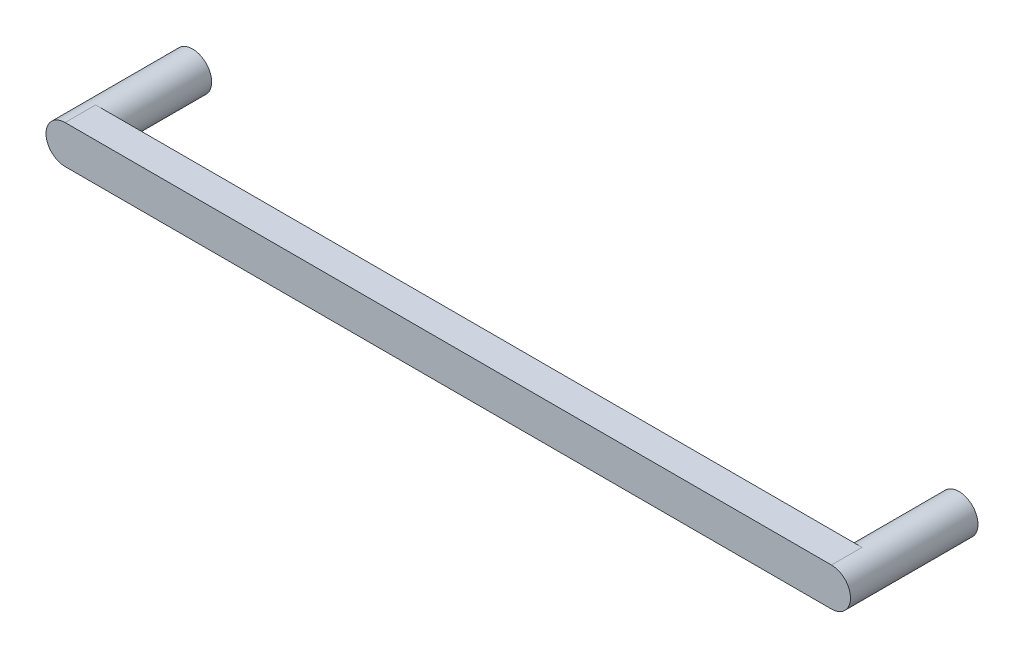
SolidWorks part; units mm, degrees
material "PLA 100% Infill"
ref_plane "Front Plane" through (0, 0, 0) normal (0, 0, 1) x (1, 0, 0)
ref_plane "Top Plane" through (0, 0, 0) normal (0, 1, 0) x (1, 0, 0)
ref_plane "Right Plane" through (0, 0, 0) normal (1, 0, 0) x (0, 0, -1)
sketch "Sketch1" plane through (0, 0, 0) normal (0, 0, 1) x (1, 0, 0)
  line L0 (-105.4, 2.5) -> (0, 2.5) construction
  line L1 (0, 0) -> (-105.4, 0)
  line L2 (0, 0) -> (0, 5)
  line L3 (0, 5) -> (-105.4, 5)
  line L4 (-105.4, 0) -> (-105.4, 5)
  circle A2 centre (-2.5, 2.5) radius 2.5
  circle A3 centre (-102.9, 2.5) radius 2.5
  dimension "D2" = 5
  dimension "D1" = 5
  dimension "D3" = 100.4
extrude "Boss-Extrude1" add sketch "Sketch1" along normal blind 4 contours A2 | A3 L0 | L0 A3 | A3 L0 A2 L3 L4 | L0 A3 L1 A2 | A2 region at (-102.9, 3.561, 0) region at (-102.9, 1.439, 0) region at (-52.7, 3.7577, 0) region at (-52.7, 1.2423, 0) region at (-2.5, 1.439, 0)
extrude "Boss-Extrude2" add sketch "Sketch1<3>" against normal blind 12.7 contours A2 | A3
sketch "Sketch1<3>" plane through (0, 0, 0) normal (0, 0, 1) x (1, 0, 0) same geometry as "Sketch1"
